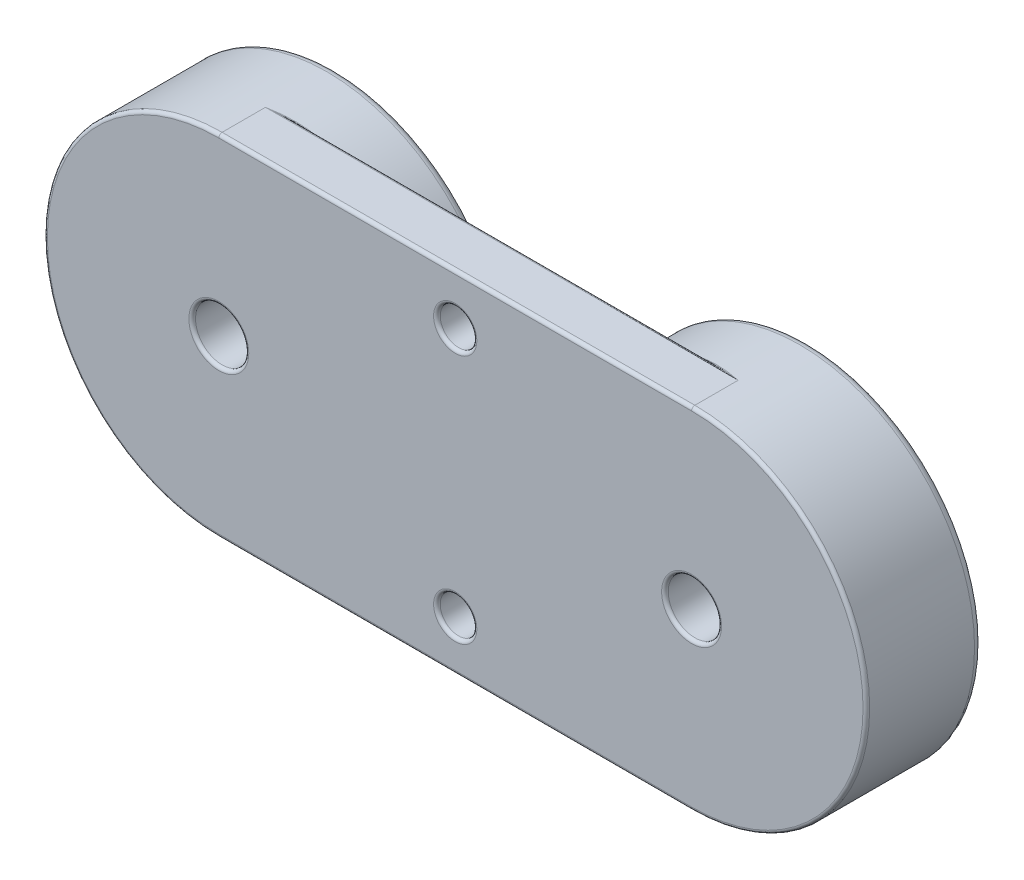
SolidWorks part; units mm, degrees
ref_plane "정면" through (0, 0, 0) normal (0, 0, 1) x (1, 0, 0)
ref_plane "윗면" through (0, 0, 0) normal (0, 1, 0) x (1, 0, 0)
ref_plane "우측면" through (0, 0, 0) normal (1, 0, 0) x (0, 0, -1)
sketch "스케치1" plane through (0, 0, 0) normal (0, 0, 1) x (1, 0, 0)
  line L0 (0, 0) -> (0, 14.1303) construction
  line L1 (-14.2, 10.5) -> (14.2, 10.5)
  line L2 (-14.2, -10.5) -> (14.2, -10.5)
  circle A0 centre (-14.2, 0) radius 1.6
  circle A1 centre (14.2, 0) radius 1.6
  circle A2 centre (-14.2, 0) radius 7.5
  circle A3 centre (14.2, 0) radius 7.5
  circle A4 centre (-14.2, 0) radius 10.5
  circle A5 centre (14.2, 0) radius 10.5
  dimension "D1" = 3.2
  dimension "D3" = 15
  dimension "D4" = 3
  dimension "D2" = 28.4
extrude "보스-돌출1" add sketch "스케치1" along normal blind 3 contours A2 A0 | A4 A2 | L2 A5 L1 A4 | A5 A3 | A3 A1 region at (0, 0, 0) region at (-6.9854, 7.2146, 0) region at (21.4146, 7.2146, 0) region at (-21.4879, 0, 0) region at (6.9121, 0, 0)
extrude "보스-돌출2" add sketch "스케치1<4>" against normal blind 4 contours A4 A2 | A5 A3 region at (-6.9854, 7.2146, 0) region at (21.4146, 7.2146, 0)
sketch "스케치1<4>" plane through (0, 0, 0) normal (0, 0, 1) x (1, 0, 0) same geometry as "스케치1"
sketch "스케치2" plane through (0, 0, 0) normal (0, 0, -1) x (-1, 0, 0)
  line L0 (0, 0) -> (0, 15.5835) construction
  line L1 (0, 0) -> (31.6797, 0) construction
  circle A0 centre (0, 7.5) radius 1.1
  circle A1 centre (0, -7.5) radius 1.1
  dimension "D1" = 2.2
  dimension "D2" = 15
extrude "컷-돌출1" cut sketch "스케치2" against normal through all
fillet "필렛1" radius 0.5 6 edges at (-3.7, 0, -4) (-6.7, 0, -4) (21.7, 0, -4) (24.7, 0, -4) (-6.7, 0, 0) (21.7, 0, 0)
fillet "필렛2" radius 0.2 14 edges at (15.8, 0, 3) (0, 10.5, 3) (24.7, 0, 3) (0, -10.5, 3) (-24.7, 0, 3) (-12.6, 0, 3) (1.1, -7.5, 3) (-1.1, 7.5, 3) (0, 10.5, 0) (-3.7, 0, 0) (0, -10.5, 0) (3.7, 0, 0) (1.1, -7.5, 0) (-1.1, 7.5, 0)
